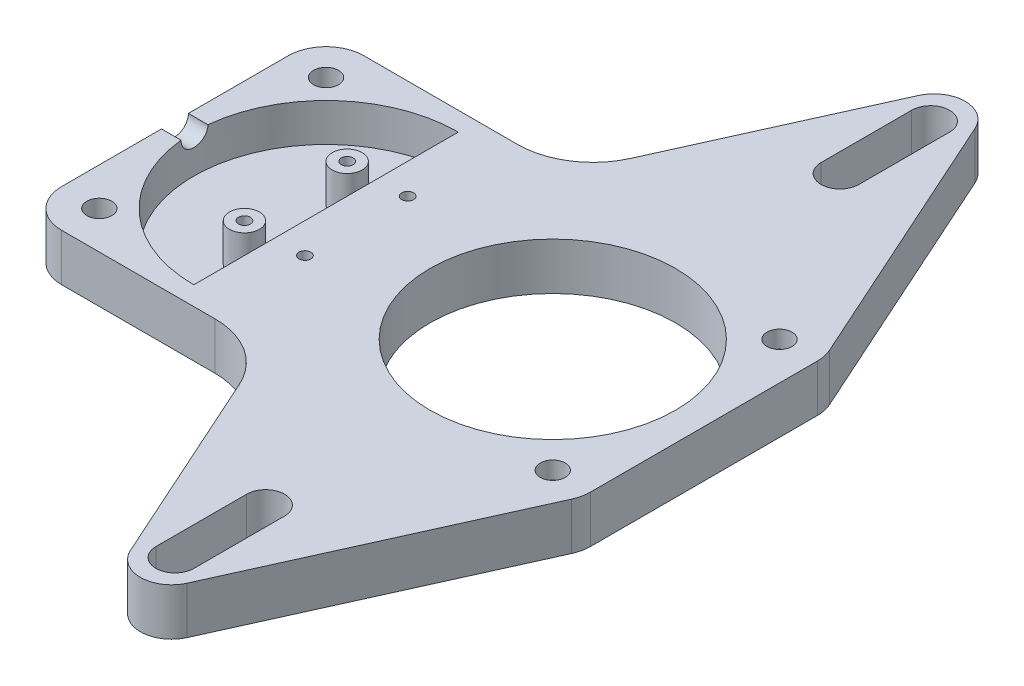
SolidWorks part; units mm, degrees
ref_plane "Front Plane" through (0, 0, 0) normal (0, 0, 1) x (1, 0, 0)
ref_plane "Top Plane" through (0, 0, 0) normal (0, 1, 0) x (1, 0, 0)
ref_plane "Right Plane" through (0, 0, 0) normal (1, 0, 0) x (0, 0, -1)
sketch "Sketch1" plane through (0, 0, 0) normal (0, 1, 0) x (1, 0, 0)
  line L0 (38.1, 19.05) -> (38.1, 25.4) construction
  line L1 (-19.05, -25.4) -> (57.15, -25.4)
  line L2 (-25.4, -19.05) -> (-25.4, 19.05)
  line L3 (-19.05, 25.4) -> (57.15, 25.4)
  line L4 (63.5, -19.05) -> (63.5, 19.05)
  line L5 (-25.4, -25.4) -> (63.5, 25.4) construction
  line L6 (-25.4, 25.4) -> (63.5, -25.4) construction
  line L7 (57.15, 0) -> (63.5, 0) construction
  line L9 (-7.62, -11.176) -> (7.62, -11.176) construction
  line L10 (-7.62, -11.176) -> (-7.62, 11.176) construction
  line L11 (-7.62, 11.176) -> (7.62, 11.176) construction
  line L12 (7.62, -11.176) -> (7.62, 11.176) construction
  line L13 (-7.62, -11.176) -> (7.62, 11.176) construction
  line L14 (-7.62, 11.176) -> (7.62, -11.176) construction
  circle A0 centre (0, 0) radius 19.05 construction
  circle A1 centre (38.1, 0) radius 19.05 construction
  circle A2 centre (38.1, 0) radius 12.7 construction
  circle A3 centre (38.1, 0) radius 20.6375
  arc A4 (-25.4, 19.05) -> (-19.05, 25.4) centre (-19.05, 19.05) cw
  arc A5 (-19.05, -25.4) -> (-25.4, -19.05) centre (-19.05, -19.05) cw
  arc A6 (57.15, -25.4) -> (63.5, -19.05) centre (57.15, -19.05) ccw
  arc A7 (57.15, 25.4) -> (63.5, 19.05) centre (57.15, 19.05) cw
  circle A8 centre (-19.05, 19.05) radius 2.1
  circle A9 centre (-19.05, -19.05) radius 2.1
  circle A10 centre (57.15, -19.05) radius 2.1
  circle A11 centre (57.15, 19.05) radius 2.1
  point P6 (19.05, 0)
  dimension "D1" = 38.1
  dimension "D2" = 38.1
  dimension "D3" = 50.8
  dimension "D7" = 25.4
  dimension "D8" = 41.275
  dimension "D9" = 6.35
  dimension "D10" = 4.2
  dimension "D4" = 88.9
  dimension "D5" = 15.24
  dimension "D6" = 22.352
extrude "Boss-Extrude1" add sketch "Sketch1" along normal blind 7.9248
sketch "Sketch2" plane through (0, 7.9248, 0) normal (0, 1, 0) x (1, 0, 0)
  line L0 (0, 22.225) -> (38.1, 22.225)
  line L1 (38.1, -22.225) -> (0, -22.225)
  arc A0 (0, 22.225) -> (0, -22.225) centre (0, 0) ccw
  arc A1 (38.1, -22.225) -> (38.1, 22.225) centre (38.1, 0) ccw
  dimension "D1" = 44.45
extrude "Cut-Extrude1" cut sketch "Sketch2" against normal offset from surface (6.4008 mm away) 1.524 up to face at (57.15, 0, 21.15)
sketch "Sketch3" plane through (0, 1.524, 0) normal (0, 1, 0) x (1, 0, 0)
  line L0 (0, 0) -> (0, 50000) construction
  line L1 (-7.62, -11.176) -> (7.62, -11.176) construction
  line L2 (-7.62, -11.176) -> (-7.62, 11.176) construction
  line L3 (-7.62, 11.176) -> (7.62, 11.176) construction
  line L4 (7.62, -11.176) -> (7.62, 11.176) construction
  line L5 (-7.62, -11.176) -> (7.62, 11.176) construction
  line L6 (-7.62, 11.176) -> (7.62, -11.176) construction
  line L7 (0, 0) -> (50000, 0) construction
  circle A0 centre (5.08, 8.636) radius 0.997
  circle A1 centre (5.08, -8.636) radius 0.997
  circle A2 centre (-5.08, 8.636) radius 0.997
  circle A3 centre (-5.08, -8.636) radius 0.997
  circle A4 centre (-5.08, 8.636) radius 2.521
  circle A5 centre (5.08, 8.636) radius 2.521
  circle A6 centre (5.08, -8.636) radius 2.521
  circle A7 centre (-5.08, -8.636) radius 2.521
  point P0 (0, 0)
  dimension "D3" = 2.54
  dimension "D4" = 2.54
  dimension "D5" = 1.9939
  dimension "D6" = 1.524
  dimension "D1" = 22.352
  dimension "D2" = 15.24
extrude "Boss-Extrude2" add sketch "Sketch3" along normal up to surface (6.4008 mm away) up to face at (19.05, 7.9248, 0)
sketch "Sketch4" plane through (0, 1.524, 0) normal (0, 1, 0) x (1, 0, 0)
  circle A0 centre (-5.08, -8.636) radius 0.9969 construction
  circle A1 centre (5.08, -8.636) radius 0.9969
  circle A2 centre (5.08, -8.636) radius 0.997
  circle A3 centre (5.08, 8.636) radius 0.9969 construction
  circle A4 centre (-5.08, 8.636) radius 0.9969 construction
  circle A5 centre (-5.08, -8.636) radius 0.997
  circle A6 centre (5.08, 8.636) radius 0.997
  circle A7 centre (-5.08, 8.636) radius 0.997
  dimension "D1" = 0
extrude "Cut-Extrude2" cut sketch "Sketch4" against normal through all
sketch "Sketch5" plane through (0, 1.524, 0) normal (0, 1, 0) x (1, 0, 0)
  line L0 (0, 22.225) -> (0, -22.225)
  line L1 (38.1, 22.225) -> (0, 22.225) construction
  line L2 (0, -22.225) -> (38.1, -22.225) construction
  line L3 (38.1, 22.225) -> (0, 22.225)
  line L4 (0, -22.225) -> (38.1, -22.225)
  circle A0 centre (38.1, 0) radius 20.6375 construction
  circle A2 centre (38.1, 0) radius 20.6375
  arc A3 (38.1, -22.225) -> (38.1, 22.225) centre (38.1, 0) ccw
  circle A4 centre (5.08, -8.636) radius 0.9969 construction
  circle A5 centre (5.08, 8.636) radius 0.9969 construction
  circle A6 centre (5.08, -8.636) radius 0.997
  circle A7 centre (5.08, 8.636) radius 0.997
  arc A8 (38.1, -22.225) -> (38.1, 22.225) centre (38.1, 0) ccw construction
extrude "Boss-Extrude3" add sketch "Sketch5" along normal up to surface (6.4008 mm away) up to face at (19.05, 7.9248, 0)
sketch "Sketch6" plane through (0, 0, 0) normal (0, -1, 0) x (1, 0, 0)
  line L0 (38.1, 0) -> (0, 0) construction
  line L1 (38.1, 0) -> (38.1, 50000) construction
  line L2 (57.15, -25.4) -> (-19.05, -25.4) construction
  line L5 (42.8625, 66.2173) -> (62.9395, 21.6586)
  line L6 (41.3079, 69.6277) -> (34.8921, 69.6277) construction
  line L7 (34.8921, 69.6277) -> (31.6842, 64.0715) construction
  line L8 (31.6842, 64.0715) -> (34.8921, 58.5152) construction
  line L9 (34.8921, 58.5152) -> (41.3079, 58.5152) construction
  line L10 (41.3079, 58.5152) -> (44.5158, 64.0715) construction
  line L11 (44.5158, 64.0715) -> (41.3079, 69.6277) construction
  line L12 (33.3375, 66.2173) -> (14.9455, 25.4)
  line L13 (57.15, 25.4) -> (14.9455, 25.4)
  line L14 (44.5158, -64.0715) -> (41.3079, -69.6277) construction
  line L15 (41.3079, -58.5152) -> (44.5158, -64.0715) construction
  line L16 (34.8921, -58.5152) -> (41.3079, -58.5152) construction
  line L17 (31.6842, -64.0715) -> (34.8921, -58.5152) construction
  line L18 (34.8921, -69.6277) -> (31.6842, -64.0715) construction
  line L19 (41.3079, -69.6277) -> (34.8921, -69.6277) construction
  line L20 (57.15, -25.4) -> (14.9455, -25.4)
  line L21 (33.3375, -66.2173) -> (14.9455, -25.4)
  line L22 (42.8625, -66.2173) -> (62.9395, -21.6586)
  arc A2 (42.8625, 66.2173) -> (38.1, 69.2951) centre (38.1, 64.0715) ccw
  arc A3 (33.3375, 66.2173) -> (38.1, 69.2951) centre (38.1, 64.0715) cw
  circle A10 centre (38.1, 64.0715) radius 6.4158 construction
  arc A11 (63.5, 19.05) -> (57.15, 25.4) centre (57.15, 19.05) ccw construction
  arc A12 (62.9395, 21.6586) -> (57.15, 25.4) centre (57.15, 19.05) ccw
  circle A13 centre (38.1, -64.0715) radius 6.4158 construction
  arc A14 (62.9395, -21.6586) -> (57.15, -25.4) centre (57.15, -19.05) cw
  arc A15 (33.3375, -66.2173) -> (38.1, -69.2951) centre (38.1, -64.0715) ccw
  arc A16 (42.8625, -66.2173) -> (38.1, -69.2951) centre (38.1, -64.0715) cw
  point P21 (38.1, 25.4)
  point P41 (38.1, -25.4)
  dimension "D1" = 9.525
  dimension "D2" = 65.744
  dimension "D5" = 11.1125
extrude "Boss-Extrude4" add sketch "Sketch6" against normal up to surface (7.9248 mm away) up to face at (-11.1125, 7.9248, 0)
sketch "Sketch7" plane through (-25.4, 0, 0) normal (-1, 0, 0) x (0, 0, 1)
  line L0 (-19.05, 7.9248) -> (19.05, 7.9248) construction
  circle A0 centre (0, 7.9248) radius 2.2606
  dimension "D1" = 4.5212
extrude "Cut-Extrude3" cut sketch "Sketch7" against normal up to next
sketch "Sketch8" plane through (0, 0, 0) normal (0, -1, 0) x (1, 0, 0)
  line L1 (-17.0004, 22.6) -> (-21.0996, 22.6)
  line L2 (-21.0996, 22.6) -> (-23.1492, 19.05)
  line L3 (-23.1492, 19.05) -> (-21.0996, 15.5)
  line L4 (-21.0996, 15.5) -> (-17.0004, 15.5)
  line L5 (-17.0004, 15.5) -> (-14.9508, 19.05)
  line L6 (-14.9508, 19.05) -> (-17.0004, 22.6)
  line L7 (-17.0004, -15.5) -> (-21.0996, -15.5)
  line L8 (-21.0996, -15.5) -> (-23.1492, -19.05)
  line L9 (-23.1492, -19.05) -> (-21.0996, -22.6)
  line L10 (-21.0996, -22.6) -> (-17.0004, -22.6)
  line L11 (-17.0004, -22.6) -> (-14.9508, -19.05)
  line L12 (-14.9508, -19.05) -> (-17.0004, -15.5)
  line L13 (59.1996, -15.5) -> (55.1004, -15.5)
  line L14 (55.1004, -15.5) -> (53.0508, -19.05)
  line L15 (53.0508, -19.05) -> (55.1004, -22.6)
  line L16 (55.1004, -22.6) -> (59.1996, -22.6)
  line L17 (59.1996, -22.6) -> (61.2492, -19.05)
  line L18 (61.2492, -19.05) -> (59.1996, -15.5)
  line L19 (59.1996, 22.6) -> (55.1004, 22.6)
  line L20 (55.1004, 22.6) -> (53.0508, 19.05)
  line L21 (53.0508, 19.05) -> (55.1004, 15.5)
  line L22 (55.1004, 15.5) -> (59.1996, 15.5)
  line L23 (59.1996, 15.5) -> (61.2492, 19.05)
  line L24 (61.2492, 19.05) -> (59.1996, 22.6)
  circle A0 centre (-19.05, 19.05) radius 3.55 construction
  circle A1 centre (-19.05, -19.05) radius 3.55 construction
  circle A2 centre (57.15, -19.05) radius 3.55 construction
  circle A3 centre (57.15, 19.05) radius 3.55 construction
  dimension "D1" = 7.1
extrude "Cut-Extrude4" cut sketch "Sketch8" against normal blind 5
fillet "Fillet1" radius 12.7 2 edges at (14.9455, 3.9624, -25.4) (14.9455, 3.9624, 25.4)
sketch "Sketch9" plane through (0, 7.9248, 0) normal (0, 1, 0) x (1, 0, 0)
  line L0 (34.9123, -63.5) -> (34.9123, -48.26)
  line L1 (41.2877, -63.5) -> (41.2877, -48.26)
  line L2 (38.1, -48.26) -> (38.1, -63.5) construction
  line L3 (57.15, -19.05) -> (57.15, 19.05) construction
  line L4 (-4.4292, 0) -> (4.4292, 0) construction
  line L5 (38.1, 48.26) -> (38.1, 63.5) construction
  line L6 (41.2877, 63.5) -> (41.2877, 48.26)
  line L7 (34.9123, 63.5) -> (34.9123, 48.26)
  line L8 (38.1, 0) -> (38.1, -63.5) construction
  arc A0 (34.9123, -63.5) -> (41.2877, -63.5) centre (38.1, -63.5) ccw
  arc A1 (34.9123, -48.26) -> (41.2877, -48.26) centre (38.1, -48.26) cw
  arc A2 (34.9123, 48.26) -> (41.2877, 48.26) centre (38.1, 48.26) ccw
  arc A3 (34.9123, 63.5) -> (41.2877, 63.5) centre (38.1, 63.5) cw
  point P11 (38.1, -55.88)
  point P21 (38.1, 55.88)
  dimension "D1" = 3.1877
  dimension "D2" = 3.1877
  dimension "D4" = 111.76
  dimension "D3" = 15.24
extrude "Cut-Extrude5" cut sketch "Sketch9" against normal blind 60.706
